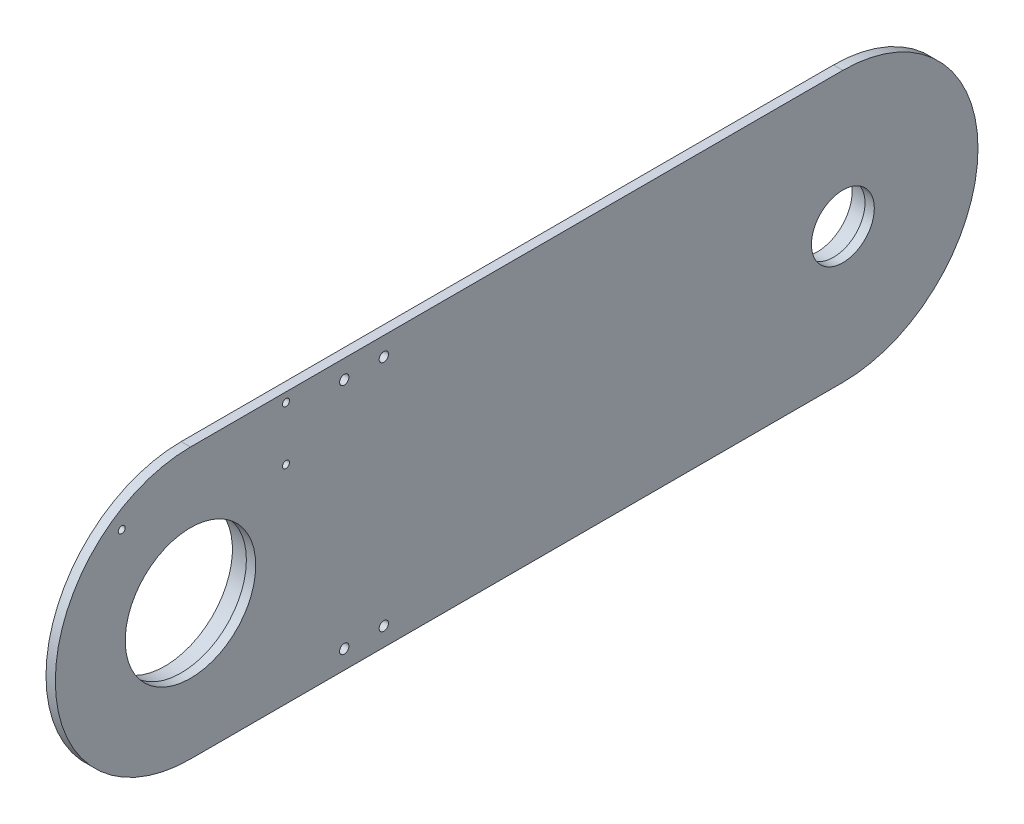
SolidWorks part; units mm, degrees
material "Zoltek Panex 33"
ref_plane "Front Plane" through (0, 0, 0) normal (0, 0, 1) x (1, 0, 0)
ref_plane "Top Plane" through (0, 0, 0) normal (0, 1, 0) x (1, 0, 0)
ref_plane "Right Plane" through (0, 0, 0) normal (1, 0, 0) x (0, 0, -1)
sketch "Sketch1" plane through (0, 0, 0) normal (1, 0, 0) x (0, 0, -1)
  line L0 (0, 0) -> (280, 0) construction
  line L1 (0, 58) -> (280, 58)
  line L2 (0, -58) -> (280, -58)
  arc A0 (0, 58) -> (0, -58) centre (0, 0) ccw
  arc A1 (280, -58) -> (280, 58) centre (280, 0) ccw
  circle A2 centre (0, 0) radius 28
  circle A3 centre (280, 0) radius 13.5
  point P3 (140, 0)
  dimension "D2" = 58
  dimension "D3" = 56
  dimension "D4" = 27
  dimension "D1" = 280
extrude "Boss-Extrude1" add sketch "Sketch1" along normal blind 4
ref_plane "Plane1" through (-7, 0, 0) normal (-1, 0, 0) x (0, 0, 1)
sketch "Sketch2" plane through (-7, 0, 0) normal (-1, 0, 0) x (0, 0, 1)
  line L0 (-140, 58) -> (-140, -58) construction
  line L1 (-280, 58) -> (0, 58) construction
  line L2 (0, -58) -> (-280, -58) construction
  circle A0 centre (0, 0) radius 29
  circle A1 centre (0, 0) radius 34
  circle A2 centre (-280, 0) radius 15
  circle A3 centre (-280, 0) radius 20
  dimension "D1" = 58
  dimension "D2" = 68
  dimension "D3" = 30
  dimension "D4" = 40
extrude "Boss-Extrude2" add sketch "Sketch2" against normal up to surface (7 mm away) up to face at (0, 0, -140)
chamfer "Chamfer1" distance 8 angle 45 2 edges at (0, 0, -34) (0, 0, -300)
sketch "Sketch3" plane through (0, 0, 0) normal (-1, 0, 0) x (0, 0, 1)
  line L0 (0, 58) -> (-73, 58) construction
  line L1 (-280, 58) -> (0, 58) construction
  line L2 (-73, 58) -> (-73, -58) construction
  line L3 (0, -58) -> (-280, -58) construction
  line L4 (-73, 58) -> (-76, 58) construction
  line L5 (-76, 58) -> (-76, -58) construction
  line L6 (-69.0931, 53.5) -> (-66, 53.5) construction
  line L7 (-66, 46.5) -> (-69.0931, 46.5) construction
  line L8 (-66, 50) -> (-73, 50) construction
  line L9 (-73, 55.8533) -> (-73, 44.1467) construction
  line L10 (-73, 0) -> (-99.886, 0) construction
  line L11 (-74.5, 58) -> (-74.5, 37.4458) construction
  arc A0 (-69.0931, 53.5) -> (-73, 55.8533) centre (-69.0931, 57.9197) cw construction
  arc A1 (-66, 53.5) -> (-66, 46.5) centre (-66, 50) cw construction
  arc A2 (-69.0931, 46.5) -> (-73, 44.1467) centre (-69.0931, 42.0803) ccw construction
  circle A3 centre (-66, 50) radius 2
  circle A4 centre (-66, -50) radius 2
  circle A5 centre (-83, -50) radius 2
  circle A6 centre (-83, 50) radius 2
  dimension "D3" = 4
  dimension "D1" = 73
  dimension "D2" = 3
  dimension "D4" = 7
  dimension "D5" = 8
  dimension "D6" = 7
extrude "Cut-Extrude1" cut sketch "Sketch3" against normal through all contours A3 | A4 | A6 | A5
sketch "Sketch4" plane through (4, 0, 0) normal (1, 0, 0) x (0, 0, -1)
  line L0 (0, 58) -> (73, 58) construction
  line L1 (280, 58) -> (0, 58) construction
  line L2 (73, 58) -> (73, 42) construction
  line L3 (73, 42) -> (-29.5, 42) construction
  line L4 (73, 58) -> (73, 54) construction
  line L5 (73, 54) -> (41, 54) construction
  line L6 (41, 54) -> (41, 31) construction
  circle A0 centre (-29.5, 42) radius 1.5
  circle A1 centre (41, 54) radius 1.5
  circle A2 centre (41, 31) radius 1.5
  dimension "D4" = 3
  dimension "D8" = 3
  dimension "D9" = 3
  dimension "D1" = 73
  dimension "D2" = 16
  dimension "D3" = 102.5
  dimension "D5" = 4
  dimension "D6" = 32
  dimension "D7" = 23
extrude "Cut-Extrude2" cut sketch "Sketch4" against normal through all
sketch "Sketch5" plane through (-7, 0, 0) normal (-1, 0, 0) x (0, 0, 1)
  line L0 (-280, 0) -> (-280, 17) construction
  circle A0 centre (-280, 17) radius 1.5
  circle A1 centre (-263, 0) radius 1.5
  circle A2 centre (-280, -17) radius 1.5
  circle A3 centre (-297, 0) radius 1.5
  point P12 (-280, 0)
  dimension "D2" = 3
  dimension "D1" = 17
  dimension "D3" = 4
extrude "Cut-Extrude3" cut sketch "Sketch5" against normal blind 5
equation "\"mini-flipper-shaft-diameter\"= 26mm"
equation "\"mini-shaft-ring-groove-diam\"= 7.8mm"
equation "\"mini-shaft-ring-groove-width\"= 1mm"
equation "\"dtCoverPlate-DistFrom-GearCent\"= 73mm"
equation "\"wormGearShaft-L\"= \"dtCoverPlate-DistFrom-GearCent\" - 27.75 + 3.75"
equation "\"D1@Sketch3\"=\"dtCoverPlate-DistFrom-GearCent\""
